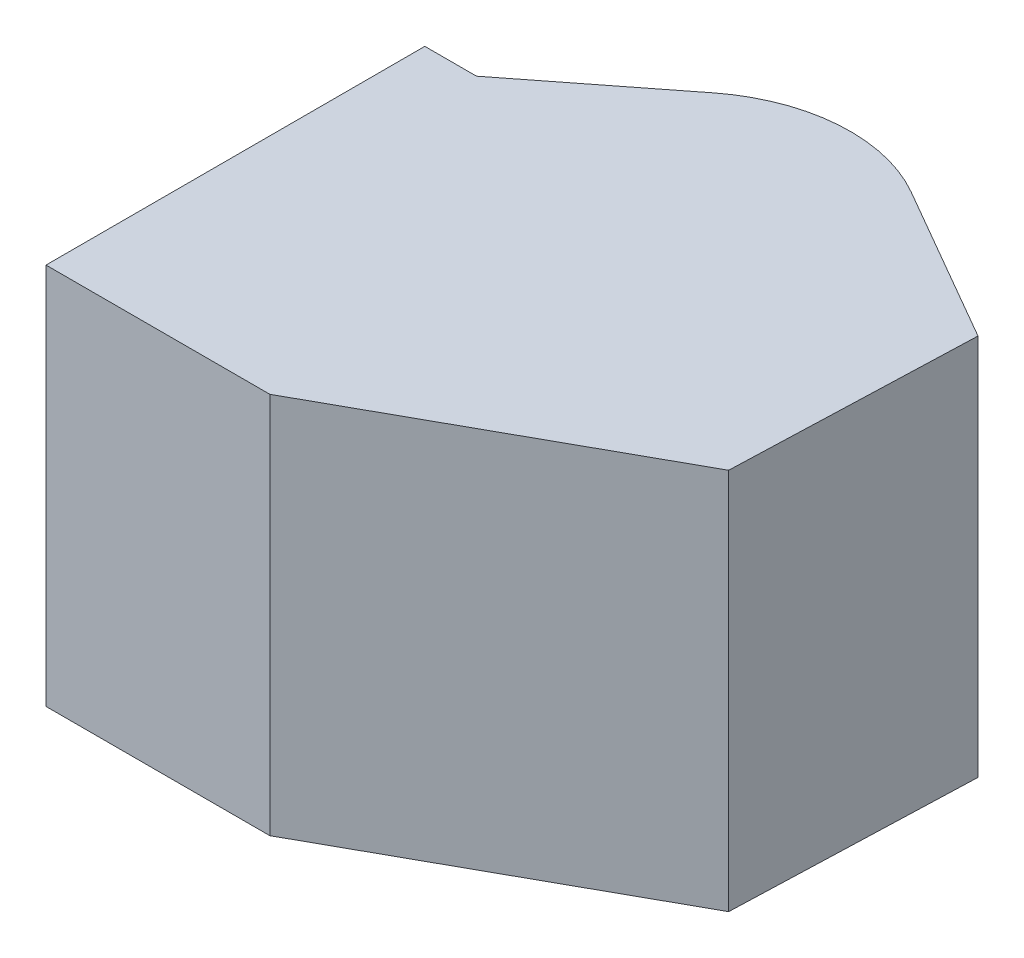
SolidWorks part; units mm, degrees
ref_plane "Front Plane" through (0, 0, 0) normal (0, 0, 1) x (1, 0, 0)
ref_plane "Top Plane" through (0, 0, 0) normal (0, 1, 0) x (1, 0, 0)
ref_plane "Right Plane" through (0, 0, 0) normal (1, 0, 0) x (0, 0, -1)
sketch "Sketch1" plane through (0, 0, 0) normal (0, 1, 0) x (1, 0, 0)
  line L0 (0, 0) -> (65, 0)
  line L1 (65, 0) -> (150.7127, 47.5113)
  line L2 (150.7127, 47.5113) -> (153.1557, 117.4687)
  line L3 (153.1557, 117.4687) -> (107.2563, 143.9687)
  line L4 (0, 0) -> (0, 110)
  line L5 (0, 110) -> (15, 110)
  line L6 (15, 110) -> (53.5902, 140.196)
  arc A0 (107.2563, 143.9687) -> (53.5902, 140.196) centre (83.2176, 102.3324) ccw
  dimension "D1" = 65
  dimension "D2" = 151
  dimension "D3" = 98
  dimension "D4" = 70
  dimension "D5" = 118
  dimension "D6" = 110
  dimension "D7" = 15
  dimension "D8" = 121
  dimension "D9" = 53
  dimension "D10" = 49
extrude "Boss-Extrude1" add sketch "Sketch1" along normal blind 55.5 and the other way blind 55.5
sketch "Sketch2" plane through (0, 0, 0) normal (-1, 0, 0) x (0, 0, 1)
  line L0 (0, -55.5) -> (0, 55.5) construction
  circle A0 centre (-55, 0) radius 45
  dimension "D1" = 90
  dimension "D2" = 55
extrude "Boss-Extrude2" add sketch "Sketch2" along normal blind 10
fillet "Fillet1" radius 3 1 edges at (0, 0, -10)
sketch "Sketch3" plane through (0, 0, 0) normal (0, 1, 0) x (1, 0, 0)
  point P0 (83.2176, 55)
move or copy body "Body-Move/Copy1" bodies to move or copy 102 copy no translate (-83.2176, 0, 55)
